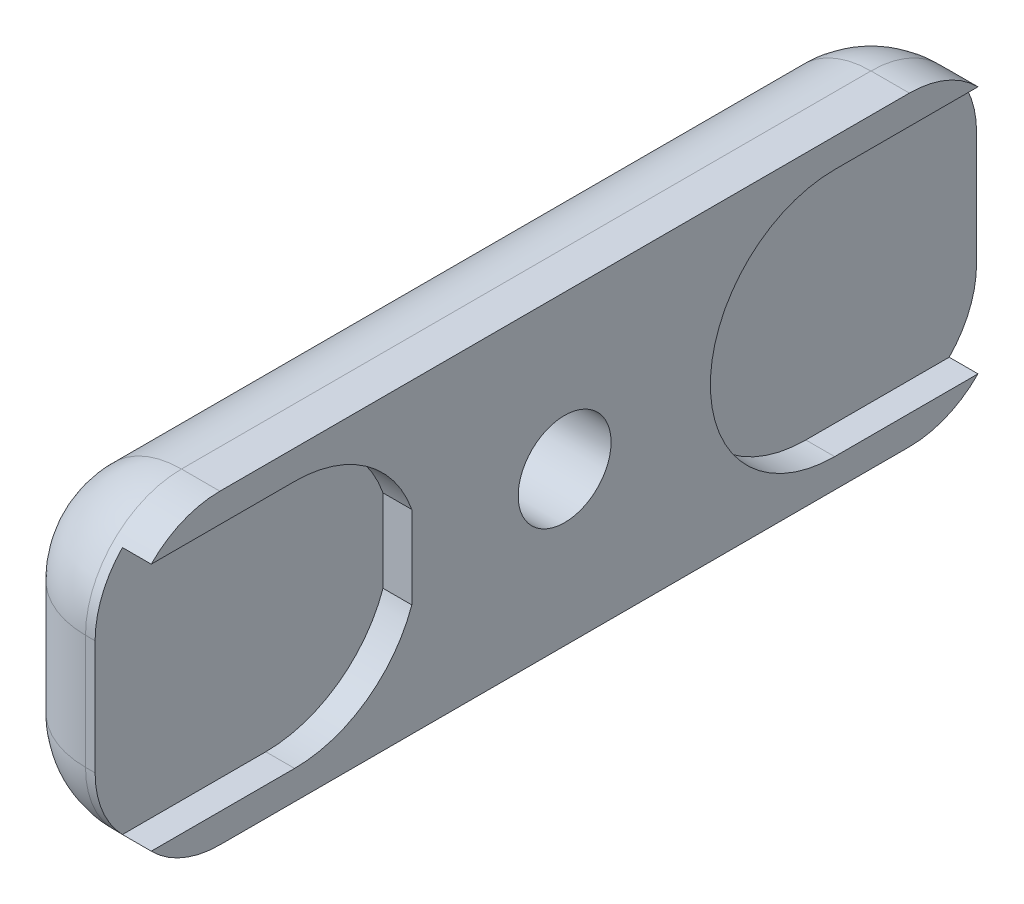
SolidWorks part; units mm, degrees
ref_plane "Front Plane" through (0, 0, 0) normal (1, 0, 0) x (0, 1, 0)
ref_plane "Top Plane" through (0, 0, 0) normal (0, 0, 1) x (0, 1, 0)
ref_plane "Right Plane" through (0, 0, 0) normal (0, 1, 0) x (-1, 0, 0)
sketch "Sketch1" plane through (0, 0, 0) normal (1, 0, 0) x (0, 1, 0)
  line L0 (-28.9545, 0) -> (33.8464, 0) construction
  line L3 (-28.9686, 19.054) -> (-28.9686, -12.7893) construction
  line L4 (0, 49.054) -> (0, -56.7378) construction
  line L6 (-28.9686, -12.7893) -> (28.9686, -12.7893)
  line L7 (44.5791, 0) -> (-44.5791, 0) construction
  line L9 (18.9686, 49.054) -> (-18.9686, 49.054)
  line L12 (-28.9686, 39.054) -> (-28.9686, 27.0474)
  line L13 (28.9686, 19.054) -> (28.9686, -12.7893) construction
  line L14 (28.9686, 39.054) -> (28.9686, 27.0474)
  line L15 (-28.9686, 19.054) -> (28.9686, 19.054) construction
  line L16 (-28.9686, 19.054) -> (28.9686, 19.054) construction
  arc A3 (-35.1108, 17.8215) -> (-28.9686, -12.7893) centre (-28.9686, 3.1323) ccw
  arc A4 (-18.9686, 49.054) -> (-28.9686, 39.054) centre (-18.9686, 39.054) ccw
  arc A5 (-35.1108, 17.8215) -> (-28.9686, 27.0474) centre (-38.9686, 27.0474) ccw
  arc A6 (35.1108, 17.8215) -> (28.9686, 27.0474) centre (38.9686, 27.0474) cw
  arc A7 (18.9686, 49.054) -> (28.9686, 39.054) centre (18.9686, 39.054) cw
  arc A8 (35.1108, 17.8215) -> (28.9686, -12.7893) centre (28.9686, 3.1323) cw
  point P20 (0, 0)
  dimension "D1" = 10
  dimension "D2" = 10
extrude "Boss-Extrude3" add sketch "Sketch1" along normal blind 14
sketch "Sketch3" plane through (14, 0, 0) normal (1, 0, 0) x (0, 1, 0)
  line L0 (-44.8903, 3.1323) -> (44.8903, 3.1323) construction
  line L2 (-28.9686, -12.7893) -> (28.9686, -12.7893) construction
  line L3 (0, -12.7893) -> (0, 49.054) construction
  line L4 (18.9686, 49.054) -> (-18.9686, 49.054) construction
  arc A3 (-35.1108, 17.8215) -> (-28.9686, -12.7893) centre (-28.9686, 3.1323) ccw construction
  arc A4 (28.9686, -12.7893) -> (35.1108, 17.8215) centre (28.9686, 3.1323) ccw construction
  circle A5 centre (0, 3.1323) radius 4.84
extrude "Cut-Extrude3" cut sketch "Sketch3" against normal blind 14.0462
sketch "Sketch4" plane through (14, 0, 0) normal (1, 0, 0) x (0, 1, 0)
  line L0 (-12.95, 49.054) -> (-12.95, 31.2677)
  line L4 (18.9686, 49.054) -> (-18.9686, 49.054) construction
  line L6 (0, 7.9723) -> (0, 31.2677) construction
  line L7 (12.95, 31.2677) -> (12.95, 49.054)
  line L8 (-12.95, 49.054) -> (12.95, 49.054)
  circle A1 centre (0, 3.1323) radius 4.84 construction
  circle A2 centre (0, 31.2677) radius 12.95 construction
  arc A3 (-12.95, 31.2677) -> (12.95, 31.2677) centre (0, 31.2677) ccw
extrude "Cut-Extrude4" cut sketch "Sketch4" against normal blind 3
sketch "Sketch5" plane through (14, 0, 0) normal (1, 0, 0) x (0, 1, 0)
  line L0 (-4, 3.1323) -> (49996, 3.1323) construction
ref_plane "Plane1" through (0, 0, 3.1323) normal (0, 0, 1) x (0, 1, 0)
mirror "Mirror1" about plane through (0, 0, 3.1323) normal (0, 0, 1) of "Boss-Extrude3", "Cut-Extrude3", "Cut-Extrude4"
sketch "Sketch6" plane through (14, 0, 0) normal (1, 0, 0) x (0, 1, 0)
  line L0 (-12.95, 49.054) -> (-18.9686, 49.054) construction
  line L1 (-15.9593, 49.054) -> (-48.7369, 49.054)
  line L2 (-15.9593, 49.054) -> (-15.9593, -48.1454)
  line L3 (-15.9593, -48.1454) -> (-48.7369, -48.1454)
  line L4 (-48.7369, 49.054) -> (-48.7369, -48.1454)
  line L5 (0, 3.1323) -> (0, 49.054) construction
  line L6 (15.9593, -48.1454) -> (48.7369, -48.1454)
  line L7 (48.7369, 49.054) -> (48.7369, -48.1454)
  line L8 (15.9593, 49.054) -> (48.7369, 49.054)
  line L9 (15.9593, 49.054) -> (15.9593, -48.1454)
extrude "Cut-Extrude6" cut sketch "Sketch6" against normal through all
fillet "Fillet1" radius 10 1 edges at (0, -15.9593, 3.1323)
fillet "Fillet2" radius 10 3 edges at (0, 5, -42.7893) (2.9289, -13.0304, -42.7893) (12, -15.9593, -42.7893)
fillet "Fillet3" radius 10 3 edges at (0, 5, 49.054) (2.9289, -13.0304, 49.054) (12, -15.9593, 49.054)
fillet "Fillet4" radius 10 5 edges at (12, 15.9593, -42.7893) (2.9289, 15.9593, -39.8604) (0, 15.9593, 3.1323) (2.9289, 15.9593, 46.1251) (12, 15.9593, 49.054)
